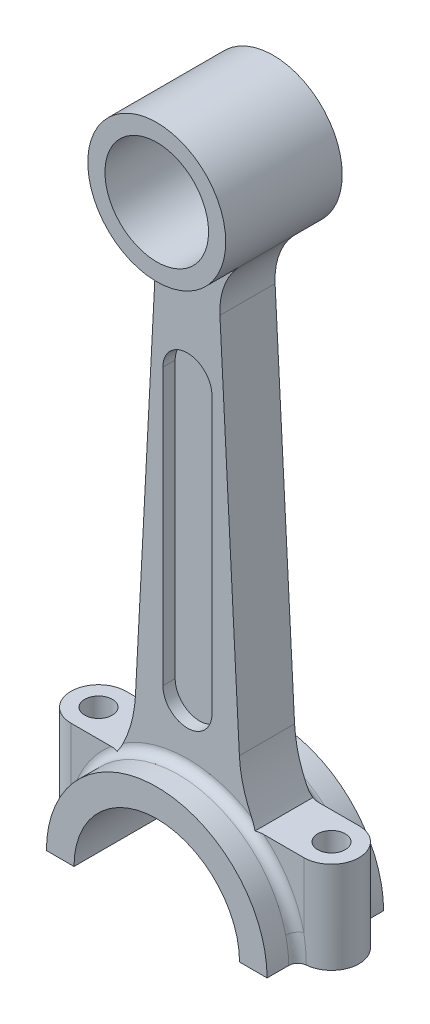
SolidWorks part; units mm, degrees
ref_plane "Front Plane" through (0, 0, 0) normal (0, 0, 1) x (1, 0, 0)
ref_plane "Top Plane" through (0, 0, 0) normal (0, 1, 0) x (1, 0, 0)
ref_plane "Right Plane" through (0, 0, 0) normal (1, 0, 0) x (0, 0, -1)
sketch "Sketch1" plane through (0, 0, 0) normal (0, 0, 1) x (1, 0, 0)
  line L0 (0, 0) -> (0, -201.2) construction
  line L1 (-10, -20.1556) -> (-17.8497, -169.9368)
  line L2 (10, -20.1556) -> (17.8497, -169.9368)
  line L4 (-36, -201.2) -> (-27, -201.2)
  line L5 (27, -201.2) -> (36, -201.2)
  circle A0 centre (0, 0) radius 22.5
  circle A1 centre (0, 0) radius 16.9
  arc A2 (27, -201.2) -> (-27, -201.2) centre (0, -201.2) ccw
  arc A3 (36, -201.2) -> (-36, -201.2) centre (0, -201.2) ccw
  dimension "D1" = 45
  dimension "D2" = 33.8
  dimension "D3" = 54
  dimension "D4" = 72
  dimension "D5" = 201.2
  dimension "D6" = 20
  dimension "D7" = 6
extrude "Boss-Extrude1" add sketch "Sketch1" along normal mid plane 38 contours A1 A0 | A3 A2 | L5 A3 L4 A2 region at (-11.5231, 18.5805, 0) region at (0, -166.005, 0)
extrude "Boss-Extrude2" add sketch "Sketch1<3>" along normal mid plane 18 contours A0 L0 A3 L2 | L0 A0 L1 A3 region at (7.1843, -100.8455, 0) region at (-7.1843, -100.8455, 0)
sketch "Sketch1<3>" plane through (0, 0, 0) normal (0, 0, 1) x (1, 0, 0) same geometry as "Sketch1"
sketch "Sketch2" plane through (0, 0, 9) normal (0, 0, 1) x (1, 0, 0)
  line L0 (0, 0) -> (0, -201.2) construction
  line L1 (0, -145.6) -> (0, -55.6) construction
  line L2 (-8, -145.6) -> (-8, -55.6)
  line L3 (8, -145.6) -> (8, -55.6)
  arc A0 (-8, -145.6) -> (8, -145.6) centre (0, -145.6) ccw
  arc A1 (8, -55.6) -> (-8, -55.6) centre (0, -55.6) ccw
  point P6 (0, -100.6)
  dimension "D2" = 8
  dimension "D1" = 90
extrude "Cut-Extrude1" cut sketch "Sketch2" against normal blind 4
mirror "Mirror1" about plane through (0, 0, 0) normal (0, 0, 1) of "Cut-Extrude1"
ref_plane "Plane1" through (0, -171.2, 0) normal (0, -1, 0) x (-1, 0, 0)
fillet "Fillet1" radius 40 2 edges at (17.8497, -169.9368, 0) (-17.8497, -169.9368, 0)
fillet "Fillet2" radius 22.5 2 edges at (10, -20.1556, 0) (-10, -20.1556, 0)
sketch "Sketch3" plane through (0, -171.2, 0) normal (0, -1, 0) x (-1, 0, 0)
  line L0 (-38, 0) -> (38, 0) construction
  line L1 (-38, 9) -> (38, 9)
  line L2 (-38, -9) -> (38, -9)
  arc A0 (-38, 9) -> (-38, -9) centre (-38, 0) ccw
  arc A1 (38, -9) -> (38, 9) centre (38, 0) ccw
  point P2 (0, 0)
  dimension "D2" = 9
  dimension "D1" = 76
extrude "Boss-Extrude3" add sketch "Sketch3" along normal blind 30
sketch "Sketch6" plane through (0, 0, 9) normal (0, 0, 1) x (1, 0, 0)
  line L1 (-27, -201.2) -> (27, -201.2)
  line L2 (-27, -201.2) -> (27, -201.2)
  arc A1 (27, -201.2) -> (-27, -201.2) centre (0, -201.2) ccw
  arc A2 (27, -201.2) -> (-27, -201.2) centre (0, -201.2) ccw
  dimension "D1" = 0
extrude "Cut-Extrude2" cut sketch "Sketch6" against normal blind 30
sketch "Sketch7" plane through (0, -171.2, 0) normal (0, 1, 0) x (1, 0, 0)
  circle A0 centre (-38, 0) radius 4.5
  circle A1 centre (38, 0) radius 4.5
  dimension "D1" = 9
  dimension "D2" = 9
extrude "Cut-Extrude3" cut sketch "Sketch7" against normal blind 30
fillet "Fillet3" radius 3 2 edges at (0, -165.2, -9) (0, -165.2, 9)
